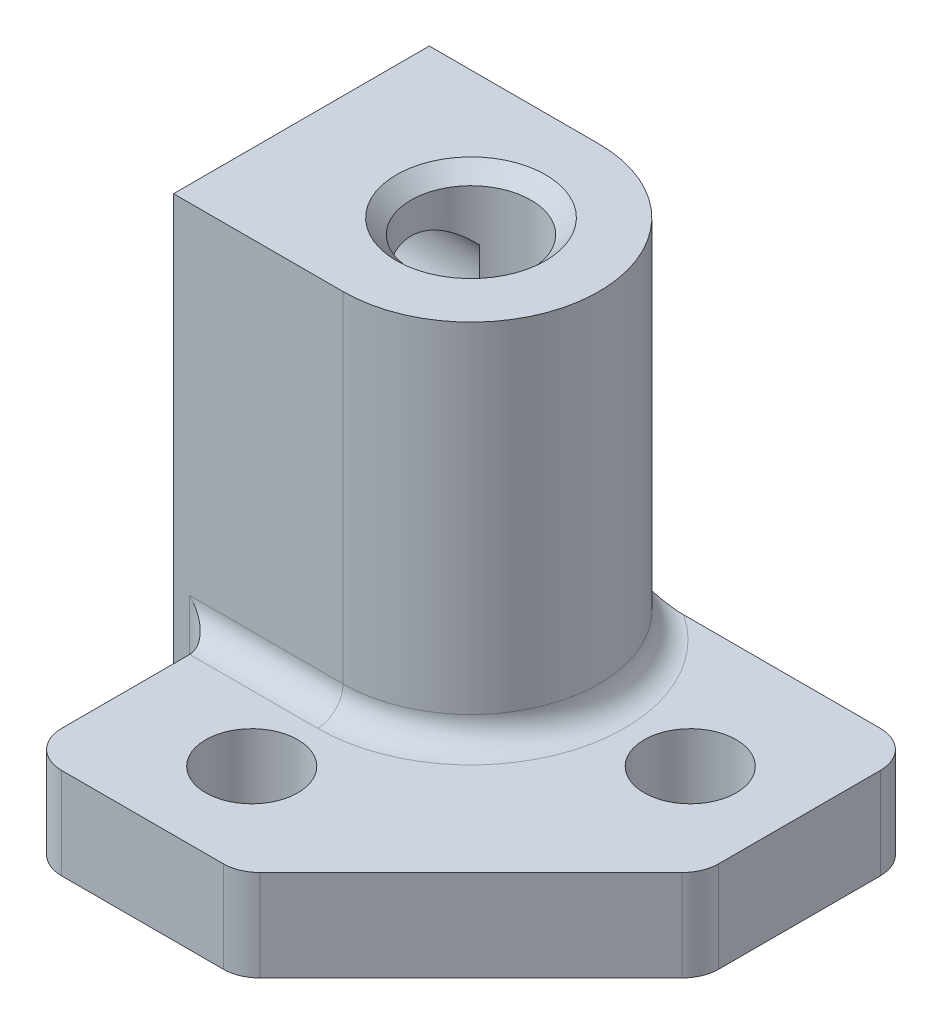
SolidWorks part; units mm, degrees
material "PLA2"
ref_plane "Front Plane" through (0, 0, 0) normal (0, 0, 1) x (1, 0, 0)
ref_plane "Top Plane" through (0, 0, 0) normal (0, 1, 0) x (1, 0, 0)
ref_plane "Right Plane" through (0, 0, 0) normal (1, 0, 0) x (0, 0, -1)
sketch "Sketch1" plane through (0, 0, 0) normal (0, 1, 0) x (1, 0, 0)
  circle A0 centre (0, 0) radius 2.0828
  circle A1 centre (0, 0) radius 4.445
  dimension "D1" = 4.1656
  dimension "D2" = 8.89
extrude "Boss-Extrude1" add sketch "Sketch1" along normal blind 12.7
sketch "Sketch2" plane through (0, 0, 0) normal (0, -1, 0) x (1, 0, 0)
  line L0 (-4.445, 0) -> (-4.445, 11.049)
  line L1 (-4.445, 11.049) -> (2.9668, 11.049)
  line L8 (2.9668, 11.049) -> (11.049, 2.9668)
  line L9 (11.049, 2.9668) -> (11.049, -4.445)
  line L10 (0, 0) -> (0, 7.62) construction
  line L11 (11.049, -4.445) -> (0, -4.445)
  line L12 (0, 0) -> (7.62, 0) construction
  circle A5 centre (0, 0) radius 4.445 construction
  arc A6 (-4.445, 0) -> (0, -4.445) centre (0, 0) ccw
  circle A7 centre (0, 7.62) radius 1.6002
  circle A8 centre (7.62, 0) radius 1.6002
  point P12 (0, 12.065)
  dimension "D1" = 3.2004
  dimension "D2" = 7.62
  dimension "D3" = 7.62
  dimension "D4" = 11.049
  dimension "D5" = 11.049
  dimension "D6" = 11.43
extrude "Boss-Extrude2" add sketch "Sketch2" along normal blind 3.175
sketch "Sketch4" plane through (0, 12.7, 0) normal (0, 1, 0) x (1, 0, 0)
  line L0 (0, 4.445) -> (-5.8928, 4.445)
  line L1 (-5.8928, 4.445) -> (-5.8928, -4.445)
  line L2 (-5.8928, -4.445) -> (0, -4.445)
  line L3 (-5.8928, 0) -> (-2.0828, 0) construction
  circle A1 centre (0, 0) radius 4.445 construction
  circle A2 centre (0, 0) radius 2.0828 construction
  circle A3 centre (0, 0) radius 2.0828 construction
  arc A4 (0, 4.445) -> (0, -4.445) centre (0, 0) ccw
  dimension "D1" = 3.81
fillet "Fillet5" radius 1.27 4 edges at (-4.445, -1.5875, 11.049) (2.9668, -1.5875, 11.049) (11.049, -1.5875, 2.9668) (11.049, -1.5875, -4.445)
extrude "Boss-Extrude3" add sketch "Sketch4" against normal up to surface (15.875 mm away) up to face at (0, -3.175, 6.0198)
chamfer "Chamfer1" distance 0.508 angle 45 1 edges at (0, 12.7, 2.0828)
sketch "Sketch3" plane through (-5.8928, 0, 0) normal (1, 0, 0) x (0, 0, -1)
  line L0 (0, 0) -> (0, 12.7) construction
  line L1 (2.0828, 12.7) -> (-2.0828, 12.7) construction
  line L2 (4.445, 12.7) -> (-4.445, 12.7) construction
  circle A0 centre (0, 8.89) radius 2.2225
  circle A1 centre (0, 2.54) radius 2.2225
  dimension "D1" = 4.445
  dimension "0.2" = 6.35
  dimension "D3" = 3.81
extrude "Cut-Extrude1" cut sketch "Sketch3" along normal blind 4.572
fillet "Fillet6" radius 0.889 3 edges at (-2.2225, 0, 4.445) (4.445, 0, 0) (-4.445, -1.5875, 4.445)
